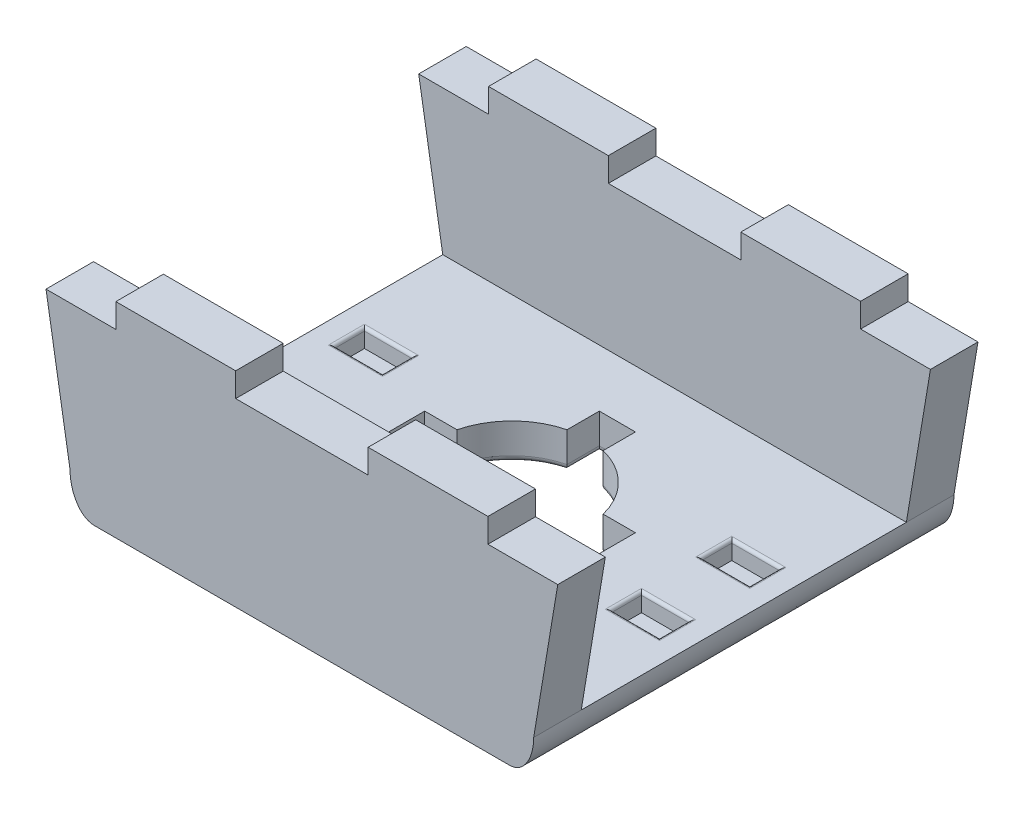
SolidWorks part; units mm, degrees
ref_plane "Front Plane" through (0, 0, 0) normal (0, 0, 1) x (1, 0, 0)
ref_plane "Top Plane" through (0, 0, 0) normal (0, 1, 0) x (1, 0, 0)
ref_plane "Right Plane" through (0, 0, 0) normal (1, 0, 0) x (0, 0, -1)
sketch "Sketch1" plane through (0, 0, 0) normal (0, 1, 0) x (1, 0, 0)
  line L0 (30.9, 34.9) -> (11, 34.9)
  line L1 (-30.9, -34.9) -> (-11, -34.9)
  line L2 (-30.9, -34.9) -> (-30.9, -27)
  line L3 (-30.9, -27) -> (-11, -27)
  line L4 (-11, -34.9) -> (-11, -27)
  line L6 (11, -34.9) -> (11, -27)
  line L7 (30.9, -27) -> (11, -27)
  line L8 (30.9, -34.9) -> (30.9, -27)
  line L9 (30.9, -34.9) -> (11, -34.9)
  line L10 (30.9, 34.9) -> (30.9, 27)
  line L11 (30.9, 27) -> (11, 27)
  line L12 (11, 34.9) -> (11, 27)
  line L13 (-11, 34.9) -> (-11, 27)
  line L14 (-30.9, 27) -> (-11, 27)
  line L15 (-30.9, 34.9) -> (-30.9, 27)
  line L16 (-30.9, 34.9) -> (-11, 34.9)
  dimension "D1" = 19.9
  dimension "D2" = 7.9
  dimension "D3" = 27
  dimension "D4" = 11
extrude "Boss-Extrude1" add sketch "Sketch1" along normal blind 4
sketch "Sketch2" plane through (0, 0, 0) normal (0, 1, 0) x (1, 0, 0)
  line L1 (42.5, 27) -> (-42.5, 27)
  line L2 (42.5, 27) -> (42.5, 34.9)
  line L3 (42.5, 34.9) -> (-42.5, 34.9)
  line L4 (-42.5, 27) -> (-42.5, 34.9)
  line L5 (42.5, 27) -> (-42.5, 34.9) construction
  line L6 (42.5, 34.9) -> (-42.5, 27) construction
  line L7 (42.5, -34.9) -> (-42.5, -34.9)
  line L8 (42.5, -34.9) -> (42.5, -27)
  line L9 (42.5, -27) -> (-42.5, -27)
  line L10 (-42.5, -34.9) -> (-42.5, -27)
  line L11 (42.5, -34.9) -> (-42.5, -27) construction
  line L12 (42.5, -27) -> (-42.5, -34.9) construction
  point P0 (0, 30.95)
  point P5 (0, -30.95)
  dimension "D1" = 85
  dimension "D2" = 0
extrude "Boss-Extrude2" add sketch "Sketch2" against normal blind 24
chamfer "Chamfer1" distance 4 distance2 24 2 edges at (42.5, -24, -30.95) (-42.5, -24, -30.95) first distance on face at (0, -24, -30.95)
chamfer "Chamfer2" distance 4 distance2 24 2 edges at (42.5, -24, 30.95) (-42.5, -24, 30.95) first distance on face at (0, -24, 30.95)
sketch "Sketch4" plane through (0, -24, 0) normal (0, -1, 0) x (1, 0, 0)
  line L1 (-38.5, -34.9) -> (38.5, -34.9)
  line L2 (-38.5, -34.9) -> (-38.5, 34.9)
  line L3 (-38.5, 34.9) -> (38.5, 34.9)
  line L4 (38.5, -34.9) -> (38.5, 34.9)
extrude "Boss-Extrude3" add sketch "Sketch4" along normal blind 6
fillet "Fillet1" radius 6 2 edges at (38.5, -30, 0) (-38.5, -30, 0) second distance 4 first distance on face at (38.5, -26, 0) first distance on face at (-38.5, -26, 0)
sketch "Sketch7" plane through (0, -30, 0) normal (0, -1, 0) x (1, 0, 0)
  line L0 (-34.5, 34.9) -> (-34.5, -34.9) construction
  line L1 (-26.5, -10) -> (-34.5, -10)
  line L2 (-26.5, -10) -> (-26.5, -5)
  line L3 (-26.5, -5) -> (-34.5, -5)
  line L4 (-34.5, -10) -> (-34.5, -5)
  line L6 (-34.5, 10) -> (-34.5, 5)
  line L7 (-26.5, 5) -> (-34.5, 5)
  line L8 (-26.5, 10) -> (-26.5, 5)
  line L9 (-26.5, 10) -> (-34.5, 10)
  line L10 (26.5, 10) -> (34.5, 10)
  line L11 (26.5, 10) -> (26.5, 5)
  line L12 (26.5, 5) -> (34.5, 5)
  line L13 (34.5, 10) -> (34.5, 5)
  line L14 (34.5, -10) -> (34.5, -5)
  line L15 (26.5, -5) -> (34.5, -5)
  line L16 (26.5, -10) -> (26.5, -5)
  line L17 (26.5, -10) -> (34.5, -10)
  dimension "D1" = 5
  dimension "D2" = 8
extrude "Cut-Extrude3" cut sketch "Sketch7" against normal through all
sketch "Sketch8" plane through (0, -30, 0) normal (0, -1, 0) x (1, 0, 0)
  line L1 (-26.5, -10) -> (-34.5, -10)
  line L2 (-26.5, -10) -> (-26.5, 10)
  line L3 (-26.5, 10) -> (-34.5, 10)
  line L4 (-34.5, -10) -> (-34.5, 10)
  line L5 (26.5, 10) -> (34.5, 10)
  line L6 (26.5, 10) -> (26.5, -10)
  line L7 (26.5, -10) -> (34.5, -10)
  line L8 (34.5, 10) -> (34.5, -10)
extrude "Boss-Extrude4" add sketch "Sketch8" against normal blind 3
sketch "Sketch9" plane through (0, -30, 0) normal (0, -1, 0) x (1, 0, 0)
  circle A0 centre (0, 0) radius 12.5
extrude "Cut-Extrude4" cut sketch "Sketch9" against normal through all
sketch "Sketch10" plane through (0, -30, 0) normal (0, -1, 0) x (1, 0, 0)
  line L0 (3, 3) -> (17.5, 3)
  line L1 (-17.5, 3) -> (-3, 3)
  line L2 (-17.5, 3) -> (-17.5, -3)
  line L3 (-17.5, -3) -> (-3, -3)
  line L4 (17.5, 3) -> (17.5, -3)
  line L5 (3, -3) -> (17.5, -3)
  line L6 (3, 3) -> (3, 17.5)
  line L7 (-3, -17.5) -> (3, -17.5)
  line L8 (-3, -17.5) -> (-3, -3)
  line L9 (-3, 17.5) -> (3, 17.5)
  line L10 (3, -17.5) -> (3, -3)
  line L11 (-3, 3) -> (-3, 17.5)
  point P0 (0, 0)
  point P6 (0, 0)
  dimension "D1" = 35
  dimension "D2" = 6
  dimension "D3" = 35
  dimension "D4" = 6
extrude "Cut-Extrude5" cut sketch "Sketch10" against normal through all contours L7 L10 L5 L4 L0 L6 L9 L11 L1 L2 L3 L8
fillet "Fillet2" radius 1 16 edges at (-14.8173, -30, 3) (-17.5, -30, 0) (-14.8173, -30, -3) (-8.8388, -30, -8.8388) (-3, -30, -14.8173) (0, -30, -17.5) (3, -30, -14.8173) (8.8388, -30, -8.8388) (14.8173, -30, -3) (17.5, -30, 0) (14.8173, -30, 3) (8.8388, -30, 8.8388) (3, -30, 14.8173) (0, -30, 17.5) (-3, -30, 14.8173) (-8.8388, -30, 8.8388)
fillet "Fillet3" radius 0.5 16 edges at (26.5, -24, 7.5) (30.5, -24, 5) (30.5, -24, 10) (34.5, -24, 7.5) (26.5, -24, -7.5) (30.5, -24, -10) (30.5, -24, -5) (34.5, -24, -7.5) (-30.5, -24, -10) (-34.5, -24, -7.5) (-30.5, -24, -5) (-26.5, -24, -7.5) (-26.5, -24, 7.5) (-34.5, -24, 7.5) (-30.5, -24, 10) (-30.5, -24, 5)
